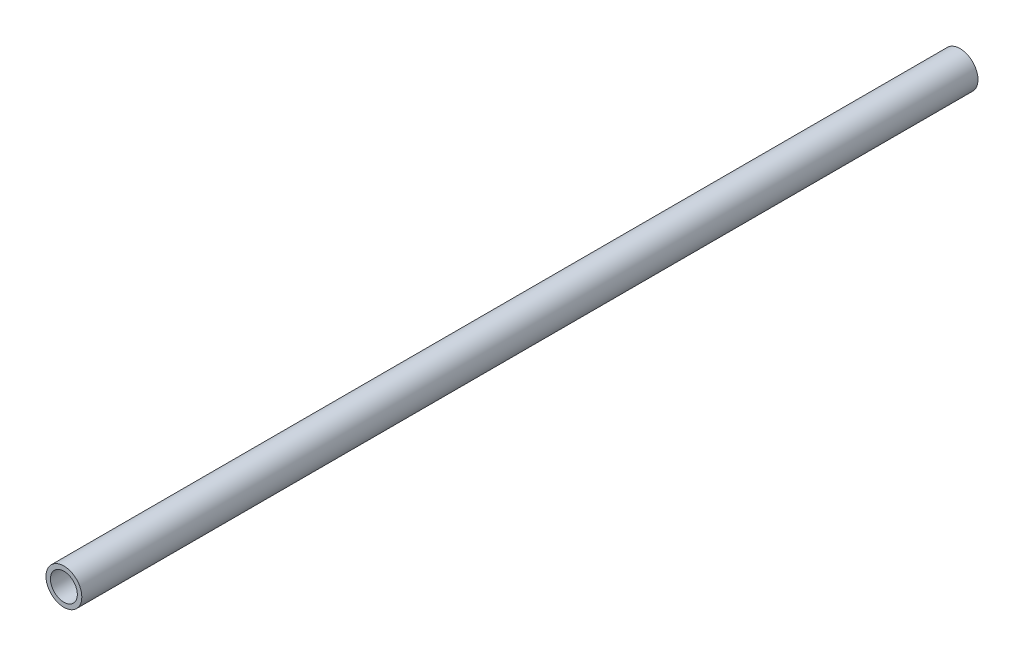
SolidWorks part; units mm, degrees
ref_plane "Front Plane" through (0, 0, 0) normal (0, 0, 1) x (1, 0, 0)
ref_plane "Top Plane" through (0, 0, 0) normal (0, 1, 0) x (1, 0, 0)
ref_plane "Right Plane" through (0, 0, 0) normal (1, 0, 0) x (0, 0, -1)
sketch "Sketch1" plane through (0, 0, 0) normal (0, 0, 1) x (1, 0, 0)
  circle A0 centre (0, 0) radius 5
  circle A1 centre (0, 0) radius 3.75
  dimension "D1" = 7.5
  dimension "D2" = 10
extrude "Boss-Extrude1" add sketch "Sketch1" along normal mid plane 250
ref_axis "Axis1" through (0, 0, 125) along (0, 0, -1)
